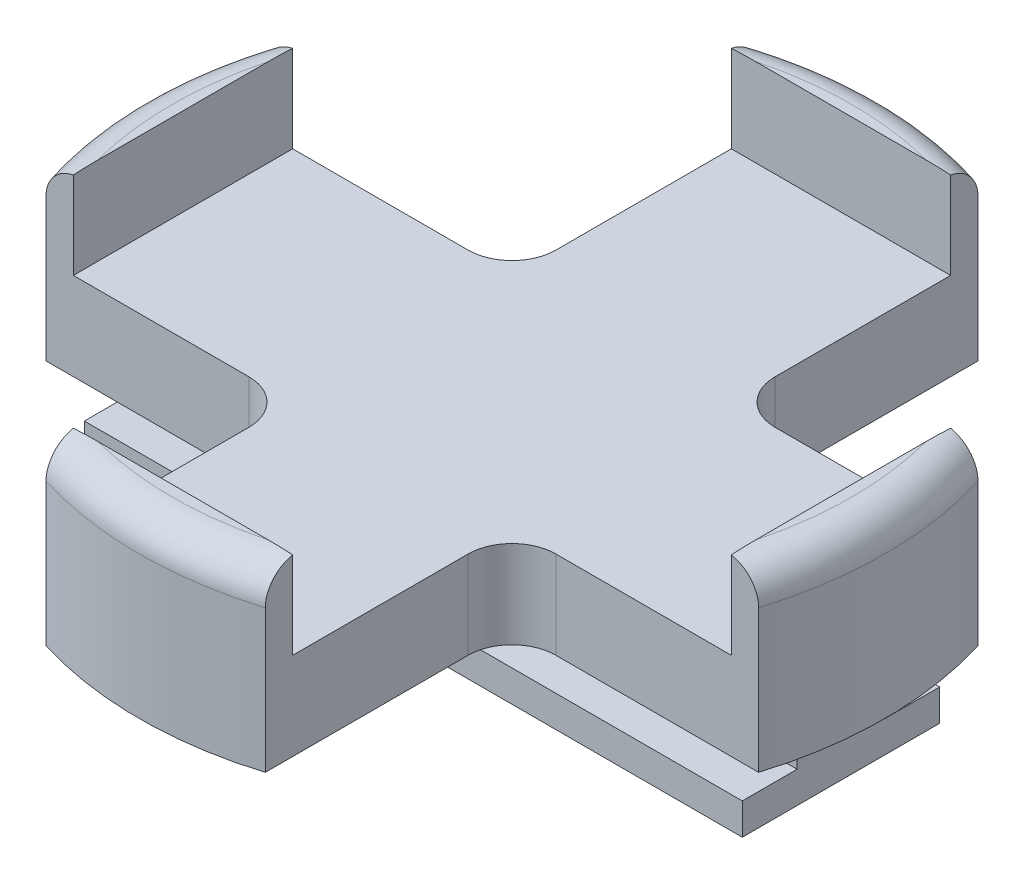
SolidWorks part; units mm, degrees
ref_plane "Front Plane" through (0, 0, 0) normal (0, 0, 1) x (1, 0, 0)
ref_plane "Top Plane" through (0, 0, 0) normal (0, 1, 0) x (1, 0, 0)
ref_plane "Right Plane" through (0, 0, 0) normal (1, 0, 0) x (0, 0, -1)
sketch "Sketch1" plane through (0, 0, 0) normal (0, 1, 0) x (1, 0, 0)
  line L0 (5, 16.2481) -> (5, 0)
  line L1 (-5, 16.2481) -> (-5, 0)
  line L2 (0, 0) -> (5.7159, 0) construction
  line L3 (-5, 0) -> (5, 0)
  line L4 (0, 4.649) -> (0, 7.2524) construction
  line L5 (-5, 15) -> (5, 15)
  arc A1 (5, 16.2481) -> (-5, 16.2481) centre (0, 0) ccw
  point P0 (0, 0)
  dimension "D1" = 5
  dimension "D2" = 5
  dimension "D3" = 15
  dimension "D4" = 17
extrude "Boss-Extrude1" add sketch "Sketch1" along normal blind 4 contours L5 L1 L3 L0 | L0 A1 L1 L5 region at (0, 0, -15.8901) region at (0, 0, -7.5)
extrude "Boss-Extrude6" add sketch "Sketch1<6>" along normal blind 8 contours L0 A1 L1 L5 region at (0, 0, -15.8901)
sketch "Sketch1<6>" plane through (0, 0, 0) normal (0, 1, 0) x (1, 0, 0) same geometry as "Sketch1"
ref_axis "Axis1" through (0, 0, 0) along (0, 1, 0)
sketch "Sketch4" plane through (0, 0, 0) normal (-1, 0, 0) x (0, 0, 1)
  line L0 (-2, 0) -> (-2, -2)
  line L2 (-2, -2) -> (-4.5, -2)
  line L3 (-4.5, -2) -> (-4.5, -3.4361)
  line L4 (-4.5, -3.4361) -> (4.5, -3.4361)
  line L5 (4.5, -3.4361) -> (4.5, -2)
  line L6 (4.5, -2) -> (2, -2)
  line L7 (2, -2) -> (2, 0)
  line L8 (-2, 0) -> (2, 0)
  dimension "D1" = 2
  dimension "D2" = 2
  dimension "D3" = 4
  dimension "D4" = 2.5
extrude "Boss-Extrude5" add sketch "Sketch4" against normal blind 15 and the other way blind 15 contours L2 L3 L4 L5 L6 L7 L8 L0
fillet "Fillet2" radius 1.5 1 edges at (0, 8, -17)
pattern_circular "CirPattern2" count 4 over 360 about axis through (0, 0, 0) along (0, 1, 0) of "Fillet2", "Boss-Extrude1", "Boss-Extrude6"
fillet "Fillet4" radius 2 4 edges at (-5, 2, 5) (5, 2, 5) (5, 2, -5) (-5, 2, -5)
